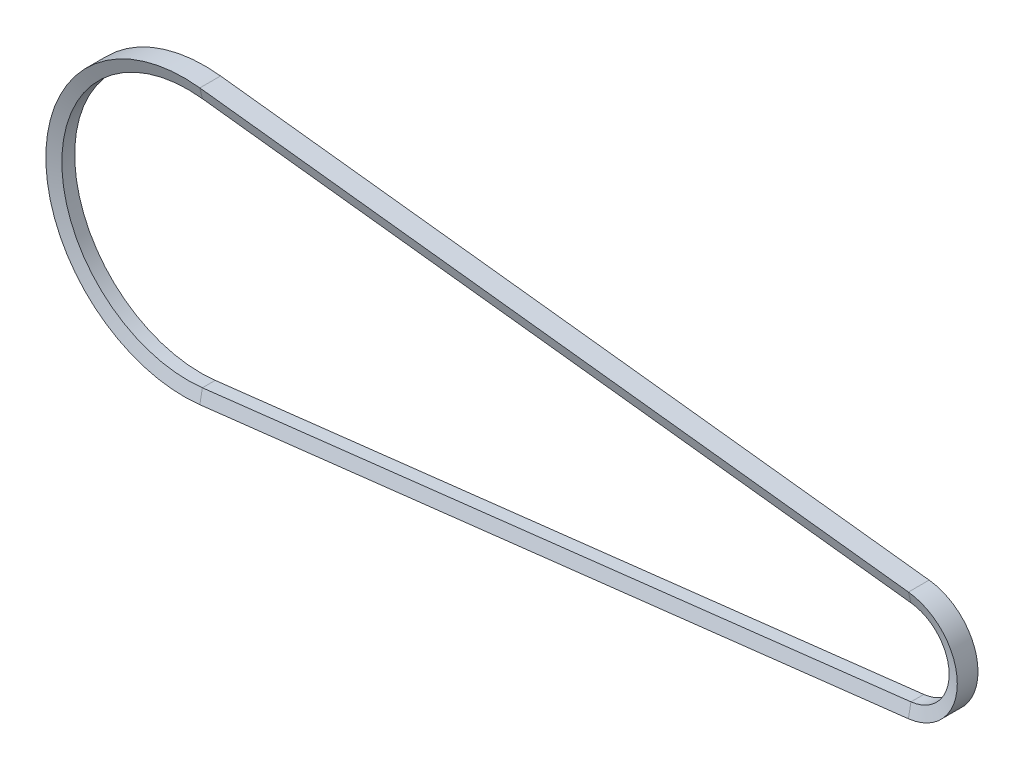
SolidWorks part; units mm, degrees
material "NEOPRENE"
ref_plane "Front Plane" through (0, 0, 0) normal (0, 0, 1) x (1, 0, 0)
ref_plane "Top Plane" through (0, 0, 0) normal (0, 1, 0) x (1, 0, 0)
ref_plane "Right Plane" through (0, 0, 0) normal (1, 0, 0) x (0, 0, -1)
sketch "Sketch1" plane through (0, 0, 0) normal (0, 0, 1) x (1, 0, 0)
  line L0 (0, 0) -> (330.2, 0) construction
  line L1 (7.3269, 63.0759) -> (333.1308, 25.2304)
  line L2 (333.1308, -25.2304) -> (7.3269, -63.0759)
  arc A0 (7.3269, 63.0759) -> (7.3269, -63.0759) centre (0, 0) ccw
  arc A1 (333.1308, -25.2304) -> (333.1308, 25.2304) centre (330.2, 0) ccw
  dimension "D2" = 127
  dimension "D3" = 50.8
  dimension "D1" = 330.2
sketch "Sketch2" plane through (0, 0, 0) normal (1, 0, 0) x (0, 0, -1)
  line L0 (-4.7625, 63.5) -> (4.7625, 63.5)
  line L1 (4.7625, 63.5) -> (2.9572, 57.9438)
  line L2 (2.9572, 57.9438) -> (-2.9572, 57.9438)
  line L3 (-2.9572, 57.9438) -> (-4.7625, 63.5)
  line L5 (0, 63.0759) -> (0, 25.2304) construction
  dimension "D1" = 5.5562
  dimension "D2" = 9.525
  dimension "D3" = 36
  dimension "D4" = 72
  dimension "D5" = 4.7625
  dimension "D6" = 63.5
sweep "Sweep1" add profiles "Sketch2" path "Sketch1"
